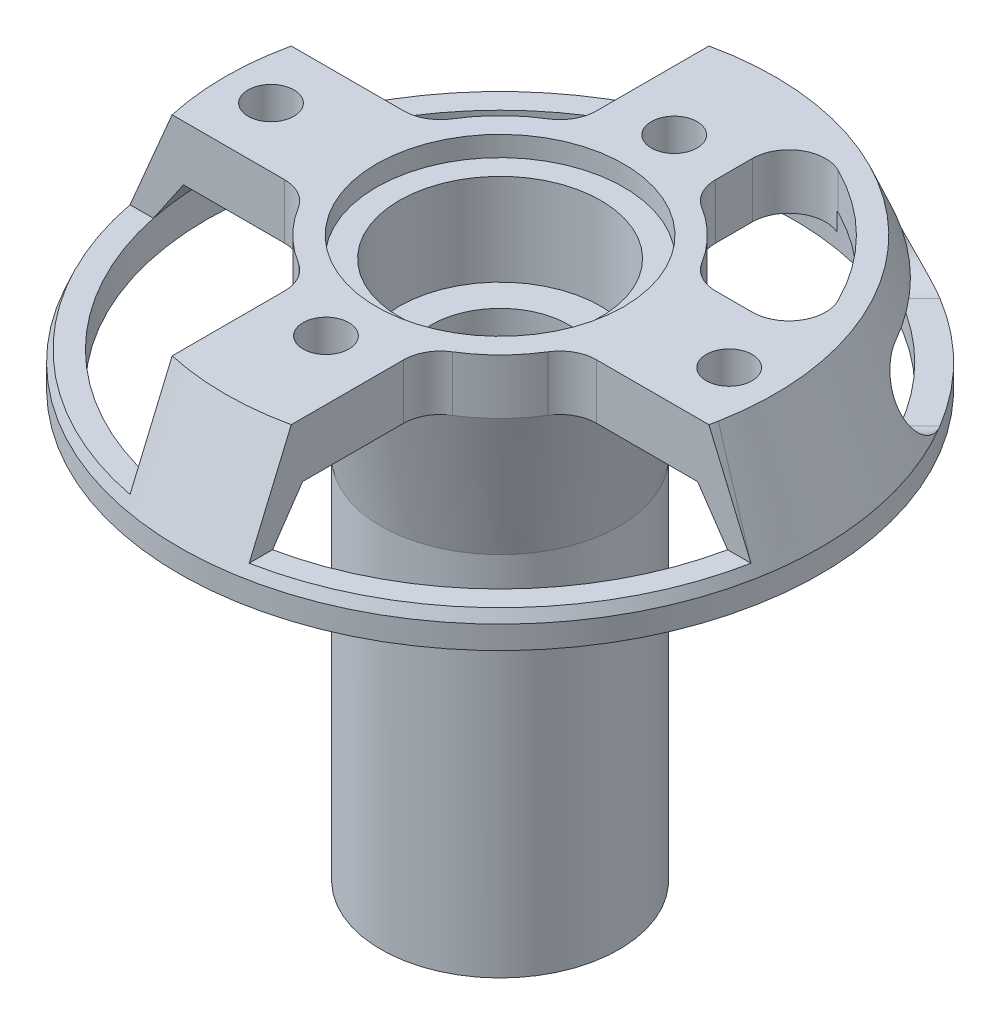
SolidWorks part; units mm, degrees
material "6061-T6 (SS)"
ref_plane "Front Plane" through (0, 0, 0) normal (0, 0, 1) x (1, 0, 0)
ref_plane "Top Plane" through (0, 0, 0) normal (0, 1, 0) x (1, 0, 0)
ref_plane "Right Plane" through (0, 0, 0) normal (1, 0, 0) x (0, 0, -1)
sketch "Sketch1" plane through (0, 0, 0) normal (0, 0, 1) x (1, 0, 0)
  line L0 (0, 15.0763) -> (0, -19.3628) construction
  line L1 (0, 0) -> (17.5, 0)
  line L2 (17.5, 0) -> (17.5, 1.25)
  line L3 (17.5, 1.25) -> (15, 7.25)
  line L4 (15, 7.25) -> (0, 7.25)
  line L5 (0, 7.25) -> (0, 0)
  dimension "D1" = 35
  dimension "D2" = 1.25
  dimension "D3" = 7.25
  dimension "D4" = 30
revolve "Bottom Base" add sketch "Sketch1" angle 360 about L0
sketch "Sketch2" plane through (0, 0, 0) normal (0, 0, 1) x (1, 0, 0)
  line L0 (16, 0) -> (16, 1.85)
  line L1 (-17.5, 0) -> (17.5, 0) construction
  line L2 (16, 1.85) -> (14.4, 4.25)
  line L3 (14.4, 4.25) -> (0, 4.25)
  line L4 (0, 4.25) -> (0, 0)
  line L5 (0, 0) -> (16, 0)
  line L6 (17.5, 1.25) -> (17.5, 0)
  line L7 (-17.5, 0) -> (-17.5, 1.25)
  line L8 (15, 7.25) -> (-15, 7.25) construction
  line L9 (17.5, 1.25) -> (17.5, 0) construction
  line L10 (-17.5, 1.25) -> (-15, 7.25)
  line L11 (15, 7.25) -> (17.5, 1.25)
  line L12 (15, 7.25) -> (17.5, 1.25) construction
  dimension "D1" = 1.5
  dimension "D2" = 3
  dimension "D3" = 1.85
  dimension "D4" = 0.6
revolve "Cut-Revolve1" cut sketch "Sketch2" angle 360 about L4
sketch "Sketch3" plane through (0, 7.25, 0) normal (0, 1, 0) x (1, 0, 0)
  circle A0 centre (0, 0) radius 6.75
  dimension "D1" = 13.5
extrude "Cut-Extrude1" cut sketch "Sketch3" against normal blind 1.1
sketch "Sketch4" plane through (0, 0, 0) normal (0, 0, 1) x (1, 0, 0)
  line L0 (-8, 4.25) -> (-6.5, -3.25)
  line L1 (-14.4, 4.25) -> (14.4, 4.25) construction
  line L2 (-6.5, -3.25) -> (-6.5, -23.25)
  line L3 (-6.5, -23.25) -> (0, -23.25)
  line L4 (0, -23.25) -> (0, 4.25)
  line L5 (0, 4.25) -> (-8, 4.25)
  line L6 (15, 7.25) -> (-15, 7.25) construction
  dimension "D1" = 8
  dimension "D2" = 30.5
  dimension "D3" = 6.5
  dimension "D4" = 20
revolve "Revolve2" add sketch "Sketch4" angle 360 about L4
sketch "Sketch5" plane through (0, 6.15, 0) normal (0, 1, 0) x (1, 0, 0)
  circle A0 centre (0, 0) radius 5.5
  dimension "D1" = 11
extrude "Bore" cut sketch "Sketch5" against normal through all
sketch "Sketch6" plane through (0, 7.25, 0) normal (0, 1, 0) x (1, 0, 0)
  line L0 (0, 0) -> (-17.5, 0) construction
  line L1 (0, 0) -> (0, 17.5) construction
  line L2 (-17.1956, 3.25) -> (-7.3101, 3.25)
  line L3 (-3.25, 17.1956) -> (-3.25, 7.3101)
  circle A0 centre (0, 0) radius 17.5 construction
  circle A1 centre (0, 0) radius 8 construction
  circle A2 centre (0, 0) radius 8 construction
  arc A3 (-17.1956, 3.25) -> (-3.25, 17.1956) centre (0, 0) cw
  arc A4 (-7.3101, 3.25) -> (-3.25, 7.3101) centre (0, 0) cw
  dimension "D1" = 6.5
  dimension "D2" = 6.5
extrude "Weight Relief" cut sketch "Sketch6" against normal offset from surface (5.4 mm away) 1.85 up to face at (-16, 0, 0)
fillet "Weight Relief Fillet" radius 2 2 edges at (-3.25, 5.75, -7.3101) (-7.3101, 5.75, -3.25)
pattern_circular "CirPattern1" count 3 every 90 about axis through (0, -23.25, 0) along (0, 1, 0) of "Weight Relief", "Weight Relief Fillet"
sketch "Sketch7" plane through (0, 7.25, 0) normal (0, 1, 0) x (1, 0, 0)
  line L0 (3.25, 13.3604) -> (3.25, 7.3101)
  line L1 (7.3101, 3.25) -> (13.3604, 3.25)
  line L2 (-3.25, 8.511) -> (-3.25, 14.6437) construction
  line L3 (14.6437, -3.25) -> (8.511, -3.25) construction
  arc A0 (3.25, 7.3101) -> (7.3101, 3.25) centre (0, 0) cw
  arc A1 (13.3604, 3.25) -> (3.25, 13.3604) centre (0, 0) ccw
  circle A2 centre (0, 0) radius 6.75 construction
  arc A3 (-4.2, 6.8088) -> (-6.8088, 4.2) centre (0, 0) ccw construction
  arc A4 (14.6437, -3.25) -> (-3.25, 14.6437) centre (0, 0) ccw construction
  dimension "D1" = 6.5
  dimension "D2" = 6.5
  dimension "D3" = 1.25
extrude "Cut-Extrude4" cut sketch "Sketch7" against normal through all
fillet "Fillet2" radius 2 4 edges at (3.25, 5.75, -7.3101) (7.3101, 5.75, -3.25) (13.3604, 5.75, -3.25) (3.25, 5.75, -13.3604)
ref_plane "Plane1" through (12.3744, 0, -12.3744) normal (0.7071, 0, -0.7071) x (0, 1, 0)
sketch "Sketch8" plane through (12.3744, 0, -12.3744) normal (0.7071, 0, -0.7071) x (0, 1, 0)
  line L0 (3.25, -4.25) -> (3.25, 4.25) construction
  line L1 (1.25, -4.25) -> (1.25, 4.25)
  line L2 (5.25, -4.25) -> (5.25, 4.25)
  line L3 (1.25, 17.5) -> (1.25, -17.5) construction
  line L4 (3.25, 0) -> (0, 0) construction
  arc A0 (1.25, -4.25) -> (5.25, -4.25) centre (3.25, -4.25) ccw
  arc A1 (5.25, 4.25) -> (1.25, 4.25) centre (3.25, 4.25) ccw
  point P2 (3.25, 0)
  point P12 (3.25, 6.25)
  point P13 (3.25, -6.25)
  dimension "D1" = 4
  dimension "D2" = 12.5
extrude "Cut-Extrude5" cut sketch "Sketch8" against normal blind 4.5
sketch "Sketch10" plane through (0, 7.25, 0) normal (0, 1, 0) x (1, 0, 0)
  line L0 (-12.5, 0) -> (12.5, 0) construction
  line L1 (0, -9.5) -> (0, 9.5) construction
  point P5 (0, 9.5)
  point P7 (12.5, 0)
  point P8 (0, -9.5)
  point P9 (-12.5, 0)
  dimension "D1" = 25
  dimension "D2" = 19
hole_wizard "M3x0.5 Tapped Hole1" positions "Sketch11" profile "Sketch13" tap size "M3x0.5" standard "ANSI Metric" end condition through all
sketch "Sketch11" plane through (0, 7.25, 0) normal (0, 1, 0) x (1, 0, 0)
  point P0 (0, 9.5)
  point P3 (12.5, 0)
  point P6 (0, -9.5)
  point P9 (-12.5, 0)
sketch "Sketch13" plane through (0, 7.25, -9.5) normal (1, 0, 0) x (0, 0, 1)
  line L0 (0, 0) -> (0, 30.5)
  line L1 (0, 30.5) -> (1.25, 30.5)
  line L2 (1.25, 30.5) -> (1.25, 0)
  line L5 (1.25, 0) -> (0, 0)
  line L11 (0, -6.35) -> (0, 107.95) construction
  dimension "Thru Tap Drill Dia." = 2.5
  dimension "Thru Tap Drill Depth" = 30.5
cosmetic thread "Hole Thread1" parameters "D2"=3
cosmetic thread "Hole Thread2" parameters "D2"=3
cosmetic thread "Hole Thread3" parameters "D2"=3
cosmetic thread "Hole Thread4" parameters "D2"=3
sketch "Sketch14" plane through (0, 6.15, 0) normal (0, 1, 0) x (1, 0, 0)
  circle A0 centre (0, 0) radius 3.75
  circle A1 centre (0, 0) radius 5.5 construction
  circle A2 centre (0, 0) radius 5.5
  dimension "D1" = 7.5
extrude "Boss-Extrude1" add sketch "Sketch14" against normal offset from surface (19.4 mm away) 5 from offset 5 up to face at (-5.5, -23.25, 0) offset against normal yes
sketch "Sketch9" [suppressed] plane through (0, 6.15, 0) normal (0, 1, 0) x (1, 0, 0)
  circle A0 centre (0, 0) radius 5
  dimension "D1" = 10
extrude "10mm Bore" [suppressed] cut sketch "Sketch9" against normal through all
equation "\"D2@Sketch6\"=\"D1@Sketch6\""
equation "\"D2@Sketch7\"=\"D1@Sketch7\""
